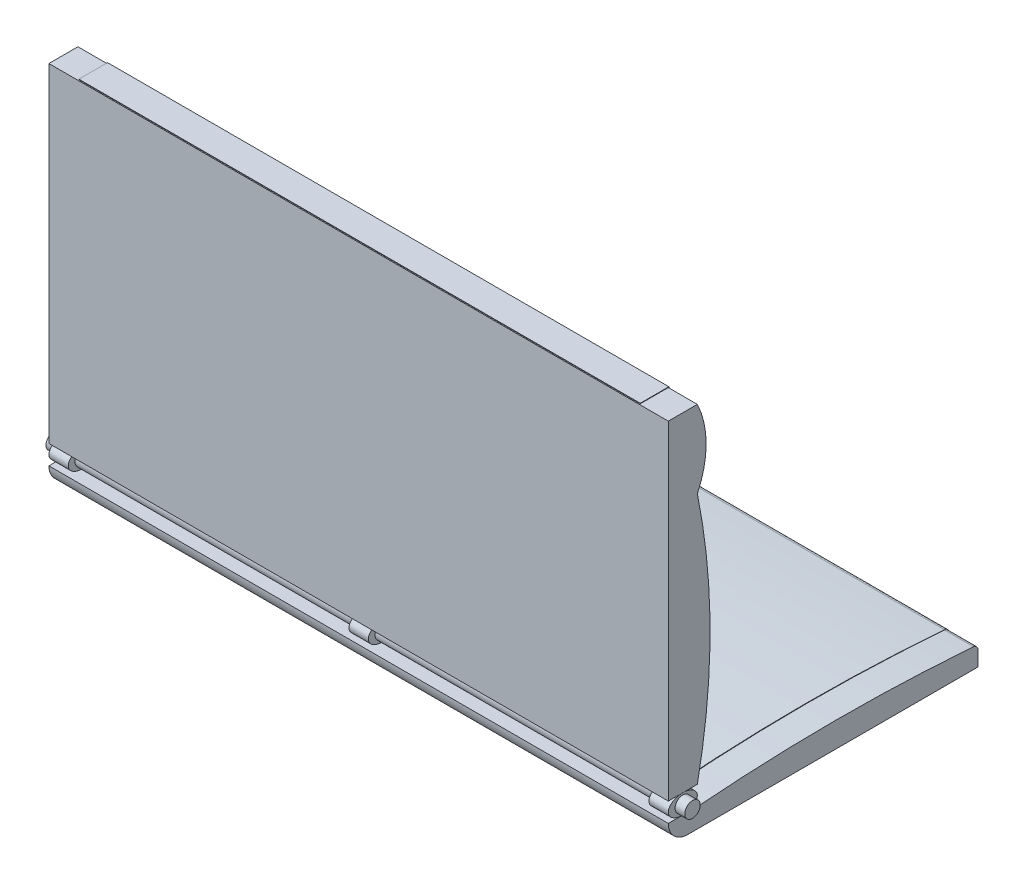
SolidWorks part; units mm, degrees
ref_plane "Front Plane" through (0, 0, 0) normal (0, 0, 1) x (1, 0, 0)
ref_plane "Top Plane" through (0, 0, 0) normal (0, 1, 0) x (1, 0, 0)
ref_plane "Right Plane" through (0, 0, 0) normal (1, 0, 0) x (0, 0, -1)
other "back"
sketch "Sketch2" plane through (0, 0, 0) normal (0, 1, 0) x (1, 0, 0)
  line L1 (-406.4, -203.2) -> (406.4, -203.2)
  line L2 (-406.4, -203.2) -> (-406.4, 203.2)
  line L3 (-406.4, 203.2) -> (406.4, 203.2)
  line L4 (406.4, -203.2) -> (406.4, 203.2)
  line L5 (-406.4, -203.2) -> (406.4, 203.2) construction
  line L6 (-406.4, 203.2) -> (406.4, -203.2) construction
  point P0 (0, 0)
extrude "Boss-Extrude1" add sketch "Sketch2" along normal blind 25.4
sketch "Sketch3" plane through (0, 25.4, 0) normal (0, 1, 0) x (1, 0, 0)
  line L0 (406.4, -203.2) -> (406.4, 203.2) construction
  line L1 (-406.4, -203.2) -> (406.4, -203.2)
  line L2 (-406.4, -203.2) -> (-406.4, -165.1)
  line L3 (-406.4, -165.1) -> (406.4, -165.1)
  line L4 (406.4, -203.2) -> (406.4, -165.1)
extrude "Boss-Extrude2" add sketch "Sketch3" along normal blind 431.8 from offset 25.4 separate body
sketch "Sketch4" plane through (406.4, 0, 0) normal (1, 0, 0) x (0, 0, -1)
  line L0 (-203.2, 50.8) -> (-203.2, 25.4) construction
  line L1 (-203.2, 25.4) -> (-165.1, 50.8) construction
  line L2 (-165.1, 50.8) -> (-165.1, 25.4) construction
  line L3 (-203.2, 25.4) -> (203.2, 25.4) construction
  line L4 (-165.1, 25.4) -> (-203.2, 50.8) construction
  line L5 (-203.2, 50.8) -> (-165.1, 50.8) construction
  ellipse E0 centre (-184.15, 38.1) end of major axis (-203.2, 38.1) minor radius 12.7
extrude "Boss-Extrude3" add sketch "Sketch4" against normal blind 25.4 separate body
sketch "Sketch6" plane through (-406.4, 0, 0) normal (-1, 0, 0) x (0, 0, 1)
  line L0 (203.2, 50.8) -> (203.2, 25.4) construction
  line L1 (203.2, 25.4) -> (165.1, 50.8) construction
  line L2 (165.1, 50.8) -> (165.1, 25.4) construction
  line L3 (-203.2, 25.4) -> (203.2, 25.4) construction
  line L4 (165.1, 25.4) -> (203.2, 50.8) construction
  line L5 (165.1, 50.8) -> (203.2, 50.8) construction
  ellipse E0 centre (184.15, 38.1) end of major axis (203.2, 38.1) minor radius 12.7
extrude "Boss-Extrude4" add sketch "Sketch6" against normal blind 25.4 separate body
sketch "Sketch7" plane through (406.4, 0, 0) normal (1, 0, 0) x (0, 0, -1)
  line L0 (-203.2, 50.8) -> (-203.2, 25.4) construction
  line L1 (-203.2, 25.4) -> (-165.1, 50.8) construction
  line L2 (-165.1, 50.8) -> (-165.1, 25.4) construction
  line L3 (-203.2, 25.4) -> (203.2, 25.4) construction
  line L4 (-165.1, 25.4) -> (-203.2, 50.8) construction
  line L5 (-203.2, 50.8) -> (-165.1, 50.8) construction
  ellipse E0 centre (-184.15, 38.1) end of major axis (-203.2, 38.1) minor radius 12.7
extrude "Boss-Extrude5" add sketch "Sketch7" along normal blind 25.4 from offset 419.1 separate body offset against normal yes
sketch "Sketch8" plane through (406.4, 0, 0) normal (1, 0, 0) x (0, 0, -1)
  circle A0 centre (-184.15, 38.1) radius 10.16
extrude "Boss-Extrude6" add sketch "Sketch8" against normal blind 838.2 from offset 12.7
sketch "Sketch9" plane through (-406.4, 0, 0) normal (-1, 0, 0) x (0, 0, 1)
  line L0 (203.2, 25.4) -> (165.1, 50.8) construction
  line L1 (165.1, 50.8) -> (165.1, 25.4) construction
  line L2 (-203.2, 25.4) -> (203.2, 25.4) construction
  line L3 (165.1, 25.4) -> (165.1, 0)
  line L4 (-203.2, 0) -> (203.2, 0) construction
  line L5 (165.1, 0) -> (-203.2, 0)
  line L6 (-203.2, 0) -> (-203.2, 25.4)
  arc A0 (-203.2, 25.4) -> (165.1, 25.4) centre (-19.05, -2245.366) cw
extrude "Boss-Extrude7" add sketch "Sketch9" against normal blind 812.8
sketch "Sketch10" plane through (-406.4, 0, 0) normal (-1, 0, 0) x (0, 0, 1)
  line L0 (165.1, 482.6) -> (165.1, 381) construction
  line L1 (165.1, 482.6) -> (165.1, 50.8) construction
  line L2 (165.1, 482.6) -> (203.2, 482.6)
  line L3 (203.2, 482.6) -> (203.2, 381)
  line L4 (203.2, 482.6) -> (203.2, 50.8) construction
  line L5 (203.2, 381) -> (165.1, 381)
  line L6 (165.1, 50.8) -> (203.2, 50.8)
  line L7 (203.2, 50.8) -> (203.2, 381)
  line L8 (203.2, 381) -> (165.1, 381)
  line L9 (165.1, 50.8) -> (203.2, 50.8)
  line L10 (203.2, 381) -> (165.1, 381)
  line L11 (203.2, 381) -> (203.2, 50.8)
  arc A0 (165.1, 482.6) -> (165.1, 381) centre (270.9064, 431.8) ccw
  arc A1 (165.1, 381) -> (165.1, 50.8) centre (972.649, 215.9) ccw
  line M2 (165.1, 50.8) -> (203.2, 50.8)
  line M3 (203.2, 50.8) -> (203.2, 482.6)
  line M4 (203.2, 482.6) -> (165.1, 482.6)
  line M5 (165.1, 482.6) -> (165.1, 50.8)
extrude "Boss-Extrude8" add sketch "Sketch10" against normal blind 812.8 contours L5 M3 M4 M5 | A1 M5 | L5 M3 M5 M2 | A0 L2 L3 L5 region at (-406.4, 431.8, 184.15) region at (-406.4, 215.9, 158.4125) region at (-406.4, 215.9, 184.15)
fillet "Fillet1" radius 25.4 1 edges at (0, 0, 203.2)
fillet "Fillet2" radius 6.35 1 edges at (0, 25.4, -203.2)
sketch "Sketch11" plane through (-406.4, 0, 0) normal (-1, 0, 0) x (0, 0, 1)
  line L0 (165.1, 482.6) -> (203.2, 482.6) construction
  line L1 (203.2, 482.6) -> (201.93, 482.6) construction
  line L2 (201.93, 482.6) -> (201.93, 483.235) construction
  line L3 (201.93, 482.6) -> (201.93, 483.235)
  line L4 (201.93, 483.235) -> (164.338, 483.235)
  line L5 (164.338, 50.1749) -> (184.15, 50.8)
  line L6 (165.1, 50.8) -> (203.2, 50.8) construction
  line L7 (201.93, 482.6) -> (201.93, 50.8)
  line L8 (201.93, 50.8) -> (184.15, 50.8)
  arc A0 (164.338, 483.235) -> (164.338, 380.5081) centre (270.4903, 431.8715) ccw
  arc A1 (164.338, 380.5081) -> (164.338, 50.1749) centre (911.4385, 215.3415) ccw
extrude "Boss-Extrude10" add sketch "Sketch11" against normal blind 736.6 from offset 38.1 separate body offset against normal yes
sketch "Sketch12" plane through (-406.4, 0, 0) normal (-1, 0, 0) x (0, 0, 1)
  line L0 (-203.2, 0.4199) -> (-203.4723, 0.4199)
  line L1 (-203.2, 19.5365) -> (-203.2, 0) construction
  line L2 (-203.4723, 0.4199) -> (-203.4723, 19.5157)
  line L3 (164.9545, 26.1401) -> (184.15, 25.4)
  line L4 (165.1, 25.4) -> (203.2, 25.4) construction
  line L5 (184.15, 25.4) -> (202.8265, 25.4)
  line L6 (-203.2, 0.4199) -> (177.698, 0.4199)
  arc A0 (-203.4723, 19.5157) -> (-197.3334, 26.1401) centre (-197.0907, 19.7584) cw
  arc A1 (-197.3334, 26.1401) -> (164.9545, 26.1401) centre (-16.1894, -2187.1393) cw
  arc A2 (177.698, 0.4199) -> (202.8265, 25.4) centre (176.9654, 26.2858) ccw
extrude "Boss-Extrude12" add sketch "Sketch12" against normal blind 736.6 from offset 38.1 separate body offset against normal yes
sketch "Sketch13" plane through (0, 0, 0) normal (0, -1, 0) x (1, 0, 0)
  line L0 (0, 0) -> (3.988, 0)
  line L1 (3.988, 0) -> (0, 5.288)
  line L2 (0, 5.288) -> (0, 0)
extrude "Boss-Extrude13" add sketch "Sketch13" along normal blind 6.35 contours L2 L0 L1
